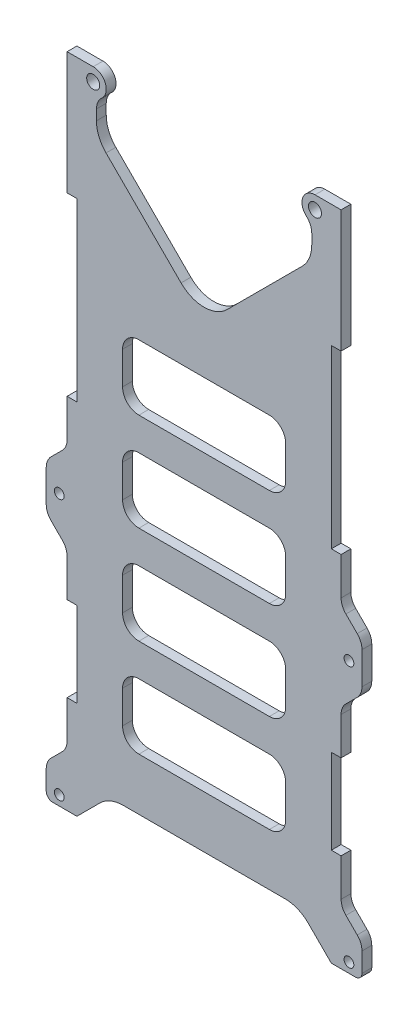
SolidWorks part; units mm, degrees
material "ABS PC"
ref_plane "Front Plane" through (0, 0, 0) normal (0, 0, 1) x (1, 0, 0)
ref_plane "Top Plane" through (0, 0, 0) normal (0, 1, 0) x (1, 0, 0)
ref_plane "Right Plane" through (0, 0, 0) normal (1, 0, 0) x (0, 0, -1)
sketch "Sketch1" plane through (0, 0, 0) normal (0, 0, 1) x (1, 0, 0)
  line L0 (46.4, -100.75) -> (39, -100.75)
  line L1 (48.4, -98.75) -> (48.4, -92.8211)
  line L2 (46.9355, -89.2855) -> (43.4645, -85.8145)
  line L3 (42, -70.75) -> (39, -70.75)
  line L4 (24.8579, -90.75) -> (0, -90.75)
  line L5 (39, -100.75) -> (31.9289, -93.6789)
  line L6 (42, -44.75) -> (42, -33.2211)
  line L7 (46.9355, -9.2855) -> (43.4645, -5.8145)
  line L8 (39, -44.75) -> (39, -70.75)
  line L9 (42, -70.75) -> (42, -82.2789)
  line L10 (48.4, -12.8211) -> (48.4, -22.6789)
  line L11 (42, -44.75) -> (39, -44.75)
  line L12 (46.9355, -26.2145) -> (43.4645, -29.6855)
  line L13 (42, -2.2789) -> (42, 9.25)
  line L14 (42, 9.25) -> (39, 9.25)
  line L15 (39, 63.25) -> (42, 63.25)
  line L16 (42, 63.25) -> (42, 100.75)
  line L17 (39, 9.25) -> (39, 63.25)
  line L18 (42, 100.75) -> (34, 100.75)
  line L19 (33, 90.0418) -> (33, 86.8921)
  line L20 (30.0711, 79.8211) -> (7.0711, 56.8211)
  line L21 (-42, -70.75) -> (-39, -70.75)
  line L22 (-39, 63.25) -> (-42, 63.25)
  line L23 (-24.8579, -90.75) -> (0, -90.75)
  line L24 (-33, 90.0418) -> (-33, 86.8921)
  line L25 (-42, -70.75) -> (-42, -82.2789)
  line L26 (-39, -100.75) -> (-31.9289, -93.6789)
  line L27 (-48.4, -98.75) -> (-48.4, -92.8211)
  line L28 (-46.9355, -89.2855) -> (-43.4645, -85.8145)
  line L29 (-42, -44.75) -> (-39, -44.75)
  line L30 (-39, 9.25) -> (-39, 63.25)
  line L31 (-42, -2.2789) -> (-42, 9.25)
  line L32 (-39, -44.75) -> (-39, -70.75)
  line L33 (-30.0711, 79.8211) -> (-7.0711, 56.8211)
  line L34 (-48.4, -12.8211) -> (-48.4, -22.6789)
  line L35 (-46.9355, -26.2145) -> (-43.4645, -29.6855)
  line L36 (-42, -44.75) -> (-42, -33.2211)
  line L37 (-42, 63.25) -> (-42, 100.75)
  line L38 (-46.9355, -9.2855) -> (-43.4645, -5.8145)
  line L39 (-42, 9.25) -> (-39, 9.25)
  line L40 (-42, 100.75) -> (-34, 100.75)
  line L41 (-46.4, -100.75) -> (-39, -100.75)
  line L42 (-25, -69.75) -> (-25, -59.75)
  line L43 (-20, -54.75) -> (20, -54.75)
  line L44 (25, -59.75) -> (25, -69.75)
  line L45 (20, -74.75) -> (-20, -74.75)
  line L46 (-25, 20.25) -> (-25, 30.25)
  line L47 (-20, 35.25) -> (20, 35.25)
  line L48 (25, 30.25) -> (25, 20.25)
  line L49 (20, 15.25) -> (-20, 15.25)
  line L50 (-25, -39.75) -> (-25, -29.75)
  line L51 (-20, -24.75) -> (20, -24.75)
  line L52 (25, -29.75) -> (25, -39.75)
  line L53 (20, -44.75) -> (-20, -44.75)
  line L54 (-25, -9.75) -> (-25, 0.25)
  line L55 (-20, 5.25) -> (20, 5.25)
  line L56 (25, 0.25) -> (25, -9.75)
  line L57 (20, -14.75) -> (-20, -14.75)
  circle A0 centre (44.4, -17.75) radius 1.5
  circle A1 centre (44.4, -97.75) radius 1.5
  arc A2 (34, 100.75) -> (31.3333, 93.7686) centre (34, 96.75) ccw
  circle A3 centre (34, 96.75) radius 2
  arc A4 (-7.0711, 56.8211) -> (7.0711, 56.8211) centre (0, 63.8921) ccw
  arc A5 (31.9289, -93.6789) -> (24.8579, -90.75) centre (24.8579, -100.75) ccw
  arc A6 (30.0711, 79.8211) -> (33, 86.8921) centre (23, 86.8921) ccw
  arc A7 (46.4, -100.75) -> (48.4, -98.75) centre (46.4, -98.75) ccw
  arc A8 (46.9355, -26.2145) -> (48.4, -22.6789) centre (43.4, -22.6789) ccw
  arc A9 (42, -2.2789) -> (43.4645, -5.8145) centre (47, -2.2789) ccw
  arc A10 (43.4645, -29.6855) -> (42, -33.2211) centre (47, -33.2211) ccw
  arc A11 (-31.3333, 93.7686) -> (-33, 90.0418) centre (-28, 90.0418) ccw
  circle A12 centre (-34, 96.75) radius 2
  circle A13 centre (-44.4, -97.75) radius 1.5
  arc A14 (-24.8579, -90.75) -> (-31.9289, -93.6789) centre (-24.8579, -100.75) ccw
  circle A15 centre (-44.4, -17.75) radius 1.5
  arc A16 (-48.4, -22.6789) -> (-46.9355, -26.2145) centre (-43.4, -22.6789) ccw
  arc A17 (-43.4645, -5.8145) -> (-42, -2.2789) centre (-47, -2.2789) ccw
  arc A18 (-46.9355, -9.2855) -> (-48.4, -12.8211) centre (-43.4, -12.8211) ccw
  arc A19 (-42, -33.2211) -> (-43.4645, -29.6855) centre (-47, -33.2211) ccw
  arc A20 (-43.4645, -85.8145) -> (-42, -82.2789) centre (-47, -82.2789) ccw
  arc A21 (-46.9355, -89.2855) -> (-48.4, -92.8211) centre (-43.4, -92.8211) ccw
  arc A22 (-31.3333, 93.7686) -> (-34, 100.75) centre (-34, 96.75) ccw
  arc A23 (-48.4, -98.75) -> (-46.4, -100.75) centre (-46.4, -98.75) ccw
  arc A24 (-33, 86.8921) -> (-30.0711, 79.8211) centre (-23, 86.8921) ccw
  arc A25 (48.4, -92.8211) -> (46.9355, -89.2855) centre (43.4, -92.8211) ccw
  arc A26 (48.4, -12.8211) -> (46.9355, -9.2855) centre (43.4, -12.8211) ccw
  arc A27 (33, 90.0418) -> (31.3333, 93.7686) centre (28, 90.0418) ccw
  arc A28 (42, -82.2789) -> (43.4645, -85.8145) centre (47, -82.2789) ccw
  arc A29 (-20, -54.75) -> (-25, -59.75) centre (-20, -59.75) ccw
  arc A30 (25, -59.75) -> (20, -54.75) centre (20, -59.75) ccw
  arc A31 (20, -74.75) -> (25, -69.75) centre (20, -69.75) ccw
  arc A32 (-25, -69.75) -> (-20, -74.75) centre (-20, -69.75) ccw
  arc A33 (-20, 35.25) -> (-25, 30.25) centre (-20, 30.25) ccw
  arc A34 (25, 30.25) -> (20, 35.25) centre (20, 30.25) ccw
  arc A35 (20, 15.25) -> (25, 20.25) centre (20, 20.25) ccw
  arc A36 (-25, 20.25) -> (-20, 15.25) centre (-20, 20.25) ccw
  arc A37 (-20, -24.75) -> (-25, -29.75) centre (-20, -29.75) ccw
  arc A38 (25, -29.75) -> (20, -24.75) centre (20, -29.75) ccw
  arc A39 (20, -44.75) -> (25, -39.75) centre (20, -39.75) ccw
  arc A40 (-25, -39.75) -> (-20, -44.75) centre (-20, -39.75) ccw
  arc A41 (-20, 5.25) -> (-25, 0.25) centre (-20, 0.25) ccw
  arc A42 (25, 0.25) -> (20, 5.25) centre (20, 0.25) ccw
  arc A43 (20, -14.75) -> (25, -9.75) centre (20, -9.75) ccw
  arc A44 (-25, -9.75) -> (-20, -14.75) centre (-20, -9.75) ccw
extrude "Boss-Extrude1" add sketch "Sketch1" along normal blind 3
